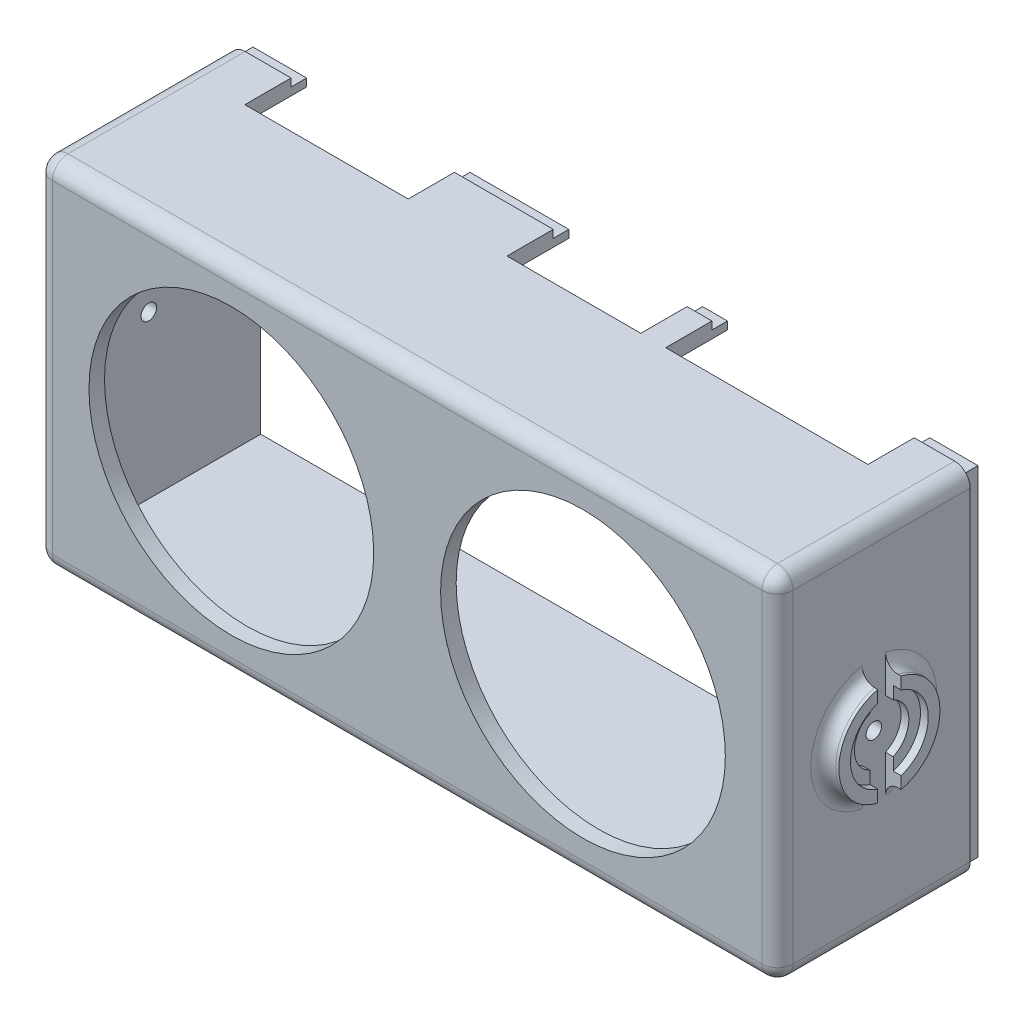
SolidWorks part; units mm, degrees
ref_plane "Спереди" through (0, 0, 0) normal (0, 0, 1) x (1, 0, 0)
ref_plane "Сверху" through (0, 0, 0) normal (0, 1, 0) x (1, 0, 0)
ref_plane "Справа" through (0, 0, 0) normal (1, 0, 0) x (0, 0, -1)
sketch "Эскиз1" plane through (0, 0, 0) normal (0, 0, 1) x (1, 0, 0)
  line L1 (-45.4, -0.2) -> (0.2, -0.2)
  line L2 (-45.4, -0.2) -> (-45.4, 20.6)
  line L3 (-45.4, 20.6) -> (0.2, 20.6)
  line L4 (0.2, -0.2) -> (0.2, 20.6)
  line L5 (1.2, 21.6) -> (-46.4, 21.6)
  line L6 (1.2, 21.6) -> (1.2, -1.2)
  line L7 (1.2, -1.2) -> (-46.4, -1.2)
  line L8 (-46.4, 21.6) -> (-46.4, -1.2)
extrude "Бобышка-Вытянуть1" add sketch "Эскиз1" along normal offset from surface (11.389 mm away) 3 offset beyond the face yes
sketch "Эскиз2" plane through (0, 0, 11.389) normal (0, 0, 1) x (1, 0, 0)
  line L1 (1.2, 21.6) -> (-46.4, 21.6)
  line L2 (1.2, 21.6) -> (1.2, -1.2)
  line L3 (1.2, -1.2) -> (-46.4, -1.2)
  line L4 (-46.4, 21.6) -> (-46.4, -1.2)
extrude "Бобышка-Вытянуть2" add sketch "Эскиз2" along normal blind 1
sketch "Эскиз3" plane through (0, 0, 12.389) normal (0, 0, 1) x (1, 0, 0)
  circle A0 centre (-11.3, 10.2) radius 9.15
  circle A1 centre (-33.9, 10.2) radius 9.15
  dimension "D1" = 18.3
extrude "Вырез-Вытянуть1" cut sketch "Эскиз3" against normal up to surface (1 mm away) up to face at (-22.6, 10.2, 11.389)
sketch "Эскиз7" plane through (0, 21.6, 0) normal (0, 1, 0) x (1, 0, 0)
  line L0 (-42.1499, -2.6711) -> (-32.2499, -2.6711) construction
  line L1 (-25.2999, -2.6711) -> (-17.2999, -2.6711) construction
  line L2 (-15.1001, -2.6711) -> (-2.7001, -2.6711) construction
  line L3 (1.2, 0) -> (-46.4, 0) construction
  line L4 (-2.4001, 0) -> (-15.4001, 0)
  line L5 (-2.4001, 0) -> (-2.4001, -2.9711)
  line L6 (-2.4001, -2.9711) -> (-15.4001, -2.9711)
  line L7 (-15.4001, 0) -> (-15.4001, -2.9711)
  line L9 (-16.9999, 0) -> (-25.5999, 0)
  line L10 (-16.9999, 0) -> (-16.9999, -2.9711)
  line L11 (-16.9999, -2.9711) -> (-25.5999, -2.9711)
  line L12 (-25.5999, 0) -> (-25.5999, -2.9711)
  line L13 (-31.9499, 0) -> (-42.4499, 0)
  line L14 (-31.9499, 0) -> (-31.9499, -2.9711)
  line L15 (-31.9499, -2.9711) -> (-42.4499, -2.9711)
  line L16 (-42.4499, 0) -> (-42.4499, -2.9711)
  dimension "D1" = 0.3
  dimension "D2" = 0.3
  dimension "D3" = 0.3
  dimension "D4" = 0.3
  dimension "D5" = 0.3
  dimension "D6" = 0.3
  dimension "D7" = 0.3
  dimension "D8" = 0.3
  dimension "D9" = 0.3
extrude "Вырез-Вытянуть2" cut sketch "Эскиз7" against normal up to surface (1 mm away) up to face at (-22.6, 20.6, 5.6945)
sketch "Эскиз8" plane through (1.2, 0, 0) normal (1, 0, 0) x (0, 0, -1)
  line L0 (-12.389, 10.2) -> (0, 10.2) construction
  line L1 (-12.389, -1.2) -> (-12.389, 21.6) construction
  line L2 (0, -1.2) -> (0, 21.6) construction
  line L3 (-6.1945, 21.6) -> (-6.1945, -1.2) construction
  line L4 (-12.389, 21.6) -> (0, 21.6) construction
  line L5 (-12.389, -1.2) -> (0, -1.2) construction
  circle A0 centre (-6.1945, 10.2) radius 1.75
  circle A1 centre (-6.1945, 10.2) radius 3.25
  dimension "D1" = 3.5
  dimension "D2" = 1.5
extrude "Бобышка-Вытянуть3" add sketch "Эскиз8" along normal blind 1
sketch "Эскиз9" plane through (2.2, 0, 0) normal (1, 0, 0) x (0, 0, -1)
  line L1 (-6.9445, 6.95) -> (-5.4445, 6.95)
  line L2 (-6.9445, 6.95) -> (-6.9445, 13.45)
  line L3 (-6.9445, 13.45) -> (-5.4445, 13.45)
  line L4 (-5.4445, 6.95) -> (-5.4445, 13.45)
  line L5 (-6.9445, 6.95) -> (-5.4445, 13.45) construction
  line L6 (-6.9445, 13.45) -> (-5.4445, 6.95) construction
  circle A0 centre (-6.1945, 10.2) radius 3.25 construction
  point P0 (-6.1945, 10.2)
  dimension "D1" = 1.5
extrude "Вырез-Вытянуть3" cut sketch "Эскиз9" against normal up to surface (1 mm away) up to face at (1.2, 10.2, 2.9445)
sketch "Эскиз10" plane through (2.2, 0, 0) normal (1, 0, 0) x (0, 0, -1)
  line L0 (-4.4445, 10.2) -> (-2.9445, 10.2) construction
  arc A1 (-5.4445, 8.6189) -> (-5.4445, 11.7811) centre (-6.1945, 10.2) ccw construction
  arc A2 (-5.4445, 7.0377) -> (-5.4445, 13.3623) centre (-6.1945, 10.2) ccw construction
  circle A3 centre (-6.1945, 10.2) radius 2.5
  point P2 (-3.6945, 10.2)
extrude "Вырез-Вытянуть6" cut sketch "Эскиз10" against normal blind 0.5
sketch "Эскиз13" plane through (1.2, 0, 0) normal (1, 0, 0) x (0, 0, -1)
  circle A0 centre (-6.1945, 10.2) radius 0.5
  dimension "D1" = 1
extrude "Вырез-Вытянуть7" cut sketch "Эскиз13" against normal up to surface (1 mm away) up to face at (0.2, 10.2, 5.6945)
sketch "Эскиз15" plane through (-46.4, 0, 0) normal (-1, 0, 0) x (0, 0, 1)
  line L0 (0, 10.2) -> (12.389, 10.2) construction
  line L1 (0, 21.6) -> (0, -1.2) construction
  line L2 (12.389, 21.6) -> (12.389, -1.2) construction
  line L3 (6.1945, 21.6) -> (6.1945, -1.2) construction
  line L4 (12.389, 21.6) -> (0, 21.6) construction
  line L5 (12.389, -1.2) -> (0, -1.2) construction
  circle A0 centre (6.1945, 10.2) radius 1.75
  circle A1 centre (6.1945, 10.2) radius 3.25
  dimension "D1" = 3.5
  dimension "D2" = 1.5
extrude "Бобышка-Вытянуть4" add sketch "Эскиз15" along normal blind 1
sketch "Эскиз16" plane through (-47.4, 0, 0) normal (-1, 0, 0) x (0, 0, 1)
  line L0 (2.9445, 10.2) -> (4.4445, 10.2) construction
  circle A0 centre (6.1945, 10.2) radius 3.25 construction
  circle A1 centre (6.1945, 10.2) radius 1.75 construction
  circle A2 centre (6.1945, 10.2) radius 2.5
  point P9 (3.6945, 10.2)
extrude "Вырез-Вытянуть8" cut sketch "Эскиз16" against normal blind 0.5
sketch "Эскиз17" plane through (-47.4, 0, 0) normal (-1, 0, 0) x (0, 0, 1)
  line L1 (6.9445, 6.95) -> (5.4445, 6.95)
  line L2 (6.9445, 6.95) -> (6.9445, 13.45)
  line L3 (6.9445, 13.45) -> (5.4445, 13.45)
  line L4 (5.4445, 6.95) -> (5.4445, 13.45)
  line L5 (6.9445, 6.95) -> (5.4445, 13.45) construction
  line L6 (6.9445, 13.45) -> (5.4445, 6.95) construction
  circle A0 centre (6.1945, 10.2) radius 3.25 construction
  point P0 (6.1945, 10.2)
  dimension "D1" = 1.5
extrude "Вырез-Вытянуть9" cut sketch "Эскиз17" against normal up to surface (1 mm away) up to face at (-46.4, 10.2, 9.4445)
sketch "Эскиз18" plane through (-46.4, 0, 0) normal (-1, 0, 0) x (0, 0, 1)
  circle A0 centre (6.1945, 10.2) radius 0.5
  dimension "D1" = 1
extrude "Вырез-Вытянуть10" cut sketch "Эскиз18" against normal up to surface (1 mm away) up to face at (-45.4, 10.2, 5.6945)
sketch "Эскиз19" plane through (0, 0, 0) normal (0, 0, -1) x (-1, 0, 0)
  line L0 (-1.2, 21.6) -> (-0.2, 20.6) construction
  line L1 (45.4, -0.2) -> (46.4, -1.2) construction
  line L2 (15.4001, 21.1) -> (15.4001, 20.6)
  line L3 (45.4, -0.2) -> (-0.2, -0.2)
  line L4 (45.4, -0.2) -> (45.4, 20.6)
  line L5 (45.4, 20.6) -> (42.4499, 20.6)
  line L6 (-0.2, -0.2) -> (-0.2, 20.6)
  line L7 (-0.7, 21.1) -> (2.4001, 21.1)
  line L8 (-0.7, 21.1) -> (-0.7, -0.7)
  line L9 (-0.7, -0.7) -> (45.9, -0.7)
  line L10 (45.9, 21.1) -> (45.9, -0.7)
  line L11 (15.4001, 20.6) -> (15.4001, 21.6) construction
  line L12 (16.9999, 21.1) -> (16.9999, 20.6)
  line L13 (16.9999, 20.6) -> (16.9999, 21.6) construction
  line L14 (2.4001, 21.1) -> (2.4001, 20.6)
  line L15 (2.4001, 20.6) -> (2.4001, 21.6) construction
  line L16 (25.5999, 21.1) -> (25.5999, 20.6)
  line L17 (25.5999, 20.6) -> (25.5999, 21.6) construction
  line L18 (31.9499, 21.1) -> (31.9499, 20.6)
  line L21 (31.9499, 20.6) -> (31.9499, 21.6) construction
  line L22 (42.4499, 21.1) -> (42.4499, 20.6)
  line L23 (42.4499, 20.6) -> (42.4499, 21.6) construction
  line L24 (42.4499, 21.1) -> (45.9, 21.1)
  line L25 (31.9499, 20.6) -> (25.5999, 20.6)
  line L26 (25.5999, 21.1) -> (31.9499, 21.1)
  line L27 (16.9999, 20.6) -> (15.4001, 20.6)
  line L28 (15.4001, 21.1) -> (16.9999, 21.1)
  line L29 (2.4001, 20.6) -> (-0.2, 20.6)
extrude "Бобышка-Вытянуть5" add sketch "Эскиз19" along normal blind 1
fillet "Скругление1" radius 0.8 4 edges at (1.2, 10.2, 9.4445) (1.2, 10.2, 2.9445) (-46.4, 10.2, 9.4445) (-46.4, 10.2, 2.9445)
fillet "Скругление2" radius 1 8 edges at (-46.4, -1.2, 6.1945) (-22.6, -1.2, 12.389) (1.2, -1.2, 6.1945) (1.2, 10.2, 12.389) (1.2, 21.6, 6.1945) (-46.4, 21.6, 6.1945) (-46.4, 10.2, 12.389) (-22.6, 21.6, 12.389)
